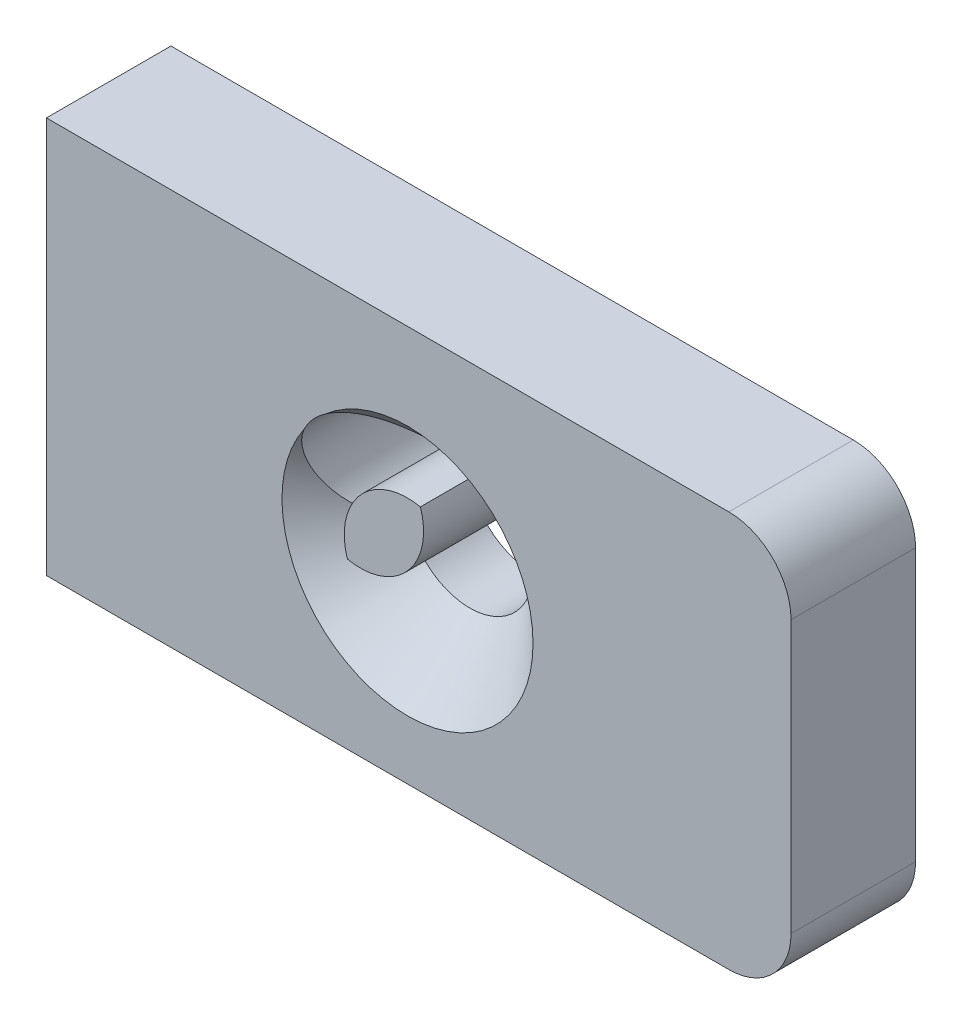
SolidWorks part; units mm, degrees
ref_plane "Front Plane" through (0, 0, 0) normal (0, 0, 1) x (1, 0, 0)
ref_plane "Top Plane" through (0, 0, 0) normal (0, 1, 0) x (1, 0, 0)
ref_plane "Right Plane" through (0, 0, 0) normal (1, 0, 0) x (0, 0, -1)
sketch "Sketch1" plane through (0, 0, 0) normal (0, 0, 1) x (1, 0, 0)
  line L1 (-57.9947, 34.0236) -> (61.6032, 34.0236)
  line L2 (-57.9947, 34.0236) -> (-57.9947, -29.6417)
  line L3 (-57.9947, -29.6417) -> (61.6032, -29.6417)
  line L4 (61.6032, 34.0236) -> (61.6032, -29.6417)
extrude "Boss-Extrude1" add sketch "Sketch1" along normal blind 20
fillet "Fillet1" radius 10 1 edges at (61.6032, 34.0236, 10)
fillet "Fillet2" radius 10 1 edges at (61.6032, -29.6417, 10)
sketch "Sketch2" plane through (0, 0, 20) normal (0, 0, 1) x (1, 0, 0)
  circle A0 centre (0, 0) radius 10.1609
  circle A1 centre (-7.5804, 6.7662) radius 10.1609
extrude "Cut-Extrude1" cut sketch "Sketch2" against normal blind 20 contours A1 A0 | A0 A1 region at (2.4335, -2.1721, 20) region at (-10.0138, 8.9383, 20)
chamfer "Chamfer1" distance 10 angle 45 1 edges at (7.5804, -6.7662, 20)
sketch "Sketch3" plane through (0, 0, 20) normal (0, 0, 1) x (1, 0, 0)
  text T0 "A"
